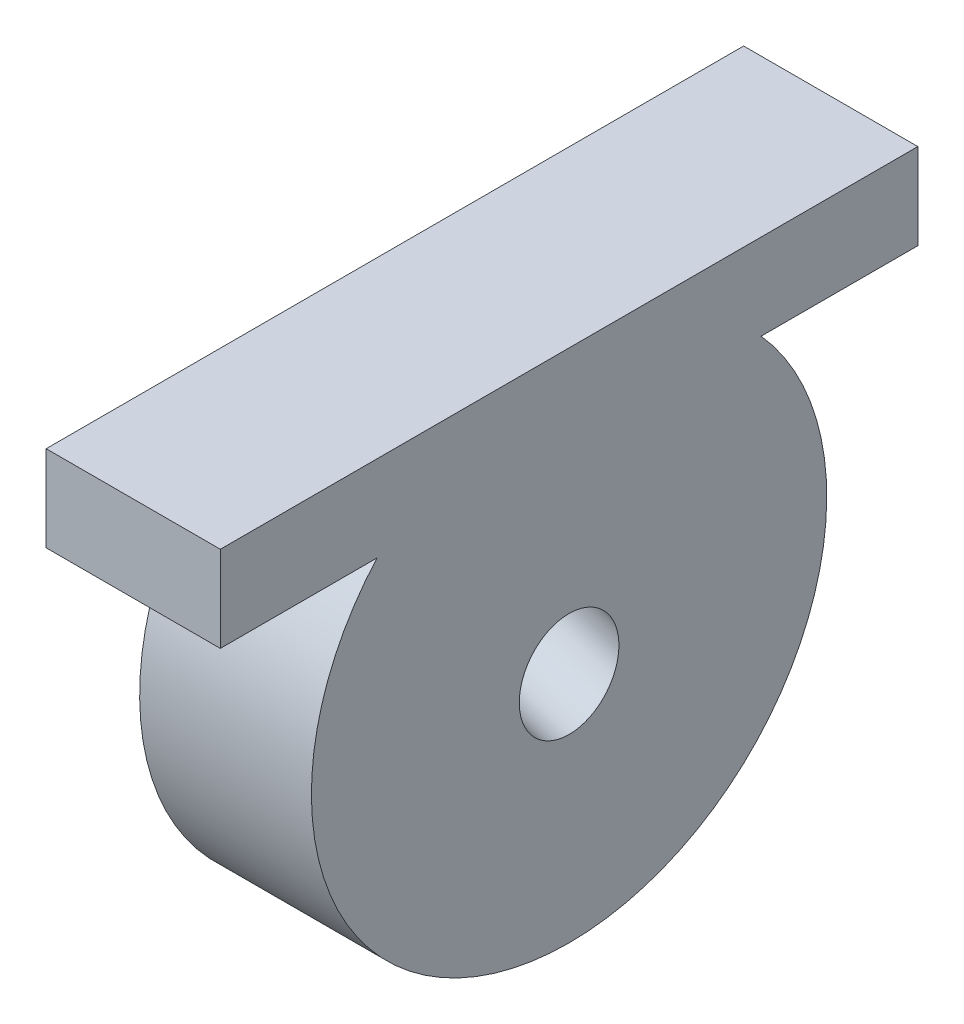
SolidWorks part; units mm, degrees
ref_plane "Front Plane" through (0, 0, 0) normal (0, 0, 1) x (1, 0, 0)
ref_plane "Top Plane" through (0, 0, 0) normal (0, 1, 0) x (1, 0, 0)
ref_plane "Right Plane" through (0, 0, 0) normal (1, 0, 0) x (0, 0, -1)
sketch "Sketch3" plane through (0, 717.6366, 0) normal (0, -1, 0) x (-1, 0, 0)
  line L0 (-524.1514, -762.9166) -> (-524.1514, -558.1792) construction
  line L1 (-524.1514, -712.1166) -> (-498.3984, -712.1166)
  line L2 (-524.1514, -712.1166) -> (-524.1514, -608.9792)
  line L3 (-524.1514, -608.9792) -> (-498.3984, -608.9792)
  line L4 (-498.3984, -712.1166) -> (-498.3984, -608.9792)
  line L5 (-498.3984, -762.9166) -> (-498.3984, -558.1792) construction
  line L6 (-524.1514, -762.9166) -> (-498.3984, -762.9166) construction
  line L7 (-524.1514, -558.1792) -> (-498.3984, -558.1792) construction
  dimension "D1" = 50.8
  dimension "D2" = 50.8
extrude "Boss-Extrude1" add sketch "Sketch3" along normal blind 12.7
sketch "Sketch4" plane through (524.1514, 0, 0) normal (1, 0, 0) x (0, 0, -1)
  line L0 (-660.5479, 717.6366) -> (-660.5479, 679.5366) construction
  line L1 (-608.9792, 717.6366) -> (-712.1166, 717.6366) construction
  circle A0 centre (-660.5479, 679.5366) radius 38.1
  dimension "D1" = 38.1
extrude "Boss-Extrude2" add sketch "Sketch4" against normal blind 25.4
ref_plane "Plane1" through (0, 0, 660.5479) normal (0, 0, 1) x (1, 0, 0)
sketch "Sketch5" plane through (0, 0, 660.5479) normal (0, 0, 1) x (1, 0, 0)
  line L0 (472.4505, 692.7093) -> (547.7665, 668.1914)
  point P2 (473.1607, 701.7644)
  point P3 (546.8438, 645.126)
  point P4 (472.4505, 692.7093)
  point P5 (547.7665, 668.1914)
sweep "Cut-Sweep1" cut path "Sketch5" circular profile diameter 14.732 parameters "D3"=14.732
